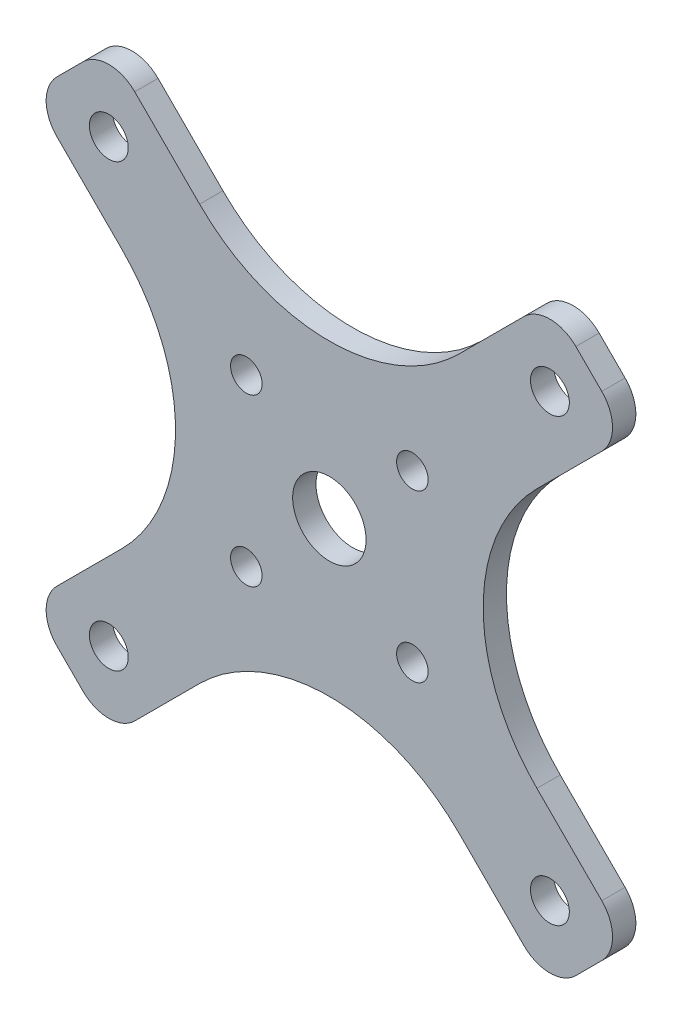
SolidWorks part; units mm, degrees
ref_plane "Front Plane" through (0, 0, 0) normal (0, 0, 1) x (1, 0, 0)
ref_plane "Top Plane" through (0, 0, 0) normal (0, 1, 0) x (1, 0, 0)
ref_plane "Right Plane" through (0, 0, 0) normal (1, 0, 0) x (0, 0, -1)
sketch "Sketch1" plane through (0, 0, 0) normal (0, 0, 1) x (1, 0, 0)
  line L0 (0, 10.6066) -> (30.052, 40.6586)
  line L1 (30.052, 40.6586) -> (40.6586, 30.052)
  line L2 (40.6586, 30.052) -> (10.6066, 0)
  line L3 (10.6066, 0) -> (40.6586, -30.052)
  line L4 (40.6586, -30.052) -> (30.052, -40.6586)
  line L5 (30.052, -40.6586) -> (0, -10.6066)
  line L6 (0, -10.6066) -> (-30.052, -40.6586)
  line L7 (-30.052, -40.6586) -> (-40.6586, -30.052)
  line L8 (-40.6586, -30.052) -> (-10.6066, 0)
  line L9 (-10.6066, 0) -> (-40.6586, 30.052)
  line L10 (-40.6586, 30.052) -> (-30.052, 40.6586)
  line L11 (-30.052, 40.6586) -> (0, 10.6066)
  line L12 (-35.3553, -35.3553) -> (35.3553, 35.3553) construction
  line L13 (-35.3553, 35.3553) -> (35.3553, -35.3553) construction
  line L14 (0, 0) -> (50, 0) construction
  circle A0 centre (0, 0) radius 5
  circle A1 centre (0, 0) radius 50 construction
  point P19 (0, 0)
  dimension "D1" = 10
  dimension "D3" = 100
  dimension "D2" = 45
  dimension "D4" = 15
extrude "Boss-Extrude1" add sketch "Sketch1" along normal mid plane 3.175
sketch "Sketch4" plane through (0, 0, 1.5875) normal (0, 0, 1) x (1, 0, 0)
  line L0 (0, 0) -> (11.3137, 11.3137) construction
  line L2 (0, 0) -> (-11.3137, -11.3137) construction
  line L4 (0, 0) -> (11.3137, -11.3137) construction
  line L6 (0, 0) -> (-11.3137, 11.3137) construction
  line L8 (10.6066, 0) -> (40.6586, 30.052) construction
  circle A0 centre (0, 0) radius 16 construction
  point P5 (11.3137, 11.3137)
  point P7 (11.3137, -11.3137)
  point P9 (-11.3137, -11.3137)
  point P11 (-11.3137, 11.3137)
  dimension "D1" = 32
hole_wizard "M4 Clearance Hole1" positions "Sketch4" profile "Sketch3" hole size "M4" standard "ANSI Metric" end condition through all
sketch "Sketch3" plane through (-11.3137, 11.3137, 1.5875) normal (1, 0, 0) x (0, -1, 0)
  line L0 (0, 0) -> (0, 3.175)
  line L1 (0, 3.175) -> (2.15, 3.175)
  line L2 (2.15, 3.175) -> (2.15, 0)
  line L5 (2.15, 0) -> (0, 0)
  line L11 (0, -6.35) -> (0, 107.95) construction
  dimension "Thru Hole Dia." = 4.3
  dimension "Thru Hole Depth" = 3.175
sketch "Sketch7" plane through (0, 0, -1.5875) normal (0, 0, -1) x (-1, 0, 0)
  line L0 (0, 0) -> (30.052, -30.052) construction
  line L3 (0, 0) -> (30.052, 30.052) construction
  line L4 (0, 0) -> (-30.052, 30.052) construction
  line L6 (0, 0) -> (-30.052, -30.052) construction
  line L8 (0, 10.6066) -> (30.052, 40.6586) construction
  line L9 (10.6066, 0) -> (40.6586, -30.052) construction
  circle A0 centre (0, 0) radius 42.5 construction
  point P0 (-30.052, 30.052)
  point P2 (30.052, 30.052)
  point P4 (30.052, -30.052)
  point P6 (-30.052, -30.052)
  dimension "D1" = 85
hole_wizard "M5 Clearance Hole1" positions "Sketch7" profile "Sketch6" hole size "M5" standard "ANSI Metric" end condition through all
sketch "Sketch6" plane through (30.052, 30.052, -1.5875) normal (1, 0, 0) x (0, 1, 0)
  line L0 (0, 0) -> (0, 3.175)
  line L1 (0, 3.175) -> (2.65, 3.175)
  line L2 (2.65, 3.175) -> (2.65, 0)
  line L5 (2.65, 0) -> (0, 0)
  line L11 (0, -6.35) -> (0, 107.95) construction
  dimension "Thru Hole Dia." = 5.3
  dimension "Thru Hole Depth" = 3.175
fillet "Fillet1" radius 25 4 edges at (-10.6066, 0, 0) (0, -10.6066, 0) (10.6066, 0, 0) (0, 10.6066, 0)
fillet "Fillet2" radius 5 8 edges at (40.6586, -30.052, 0) (30.052, -40.6586, 0) (-30.052, -40.6586, 0) (-40.6586, -30.052, 0) (-40.6586, 30.052, 0) (-30.052, 40.6586, 0) (30.052, 40.6586, 0) (40.6586, 30.052, 0)
chamfer "Chamfer1" [suppressed] distance 0.25 angle 45
